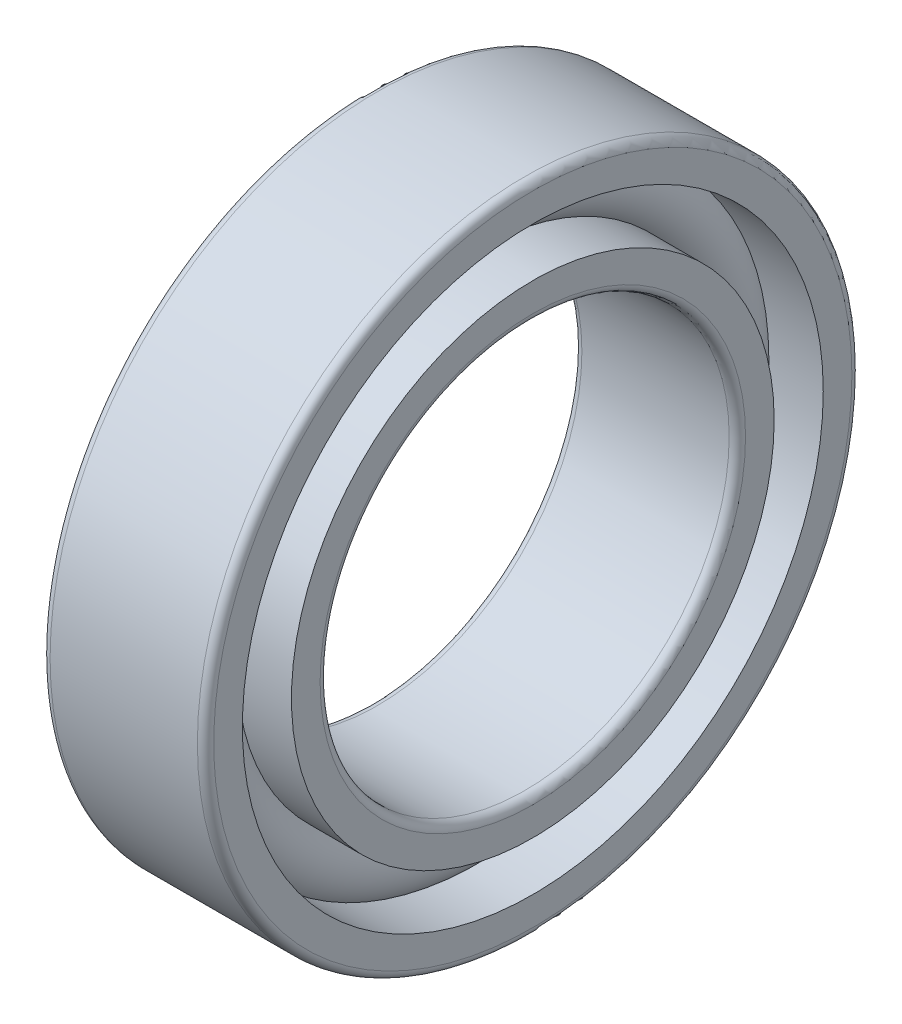
SolidWorks part; units mm, degrees
ref_plane "Plane1" through (0, 0, 0) normal (0, 0, 1) x (1, 0, 0)
ref_plane "Plane2" through (0, 0, 0) normal (0, 1, 0) x (1, 0, 0)
ref_plane "Plane3" through (0, 0, 0) normal (1, 0, 0) x (0, 0, -1)
sketch "Clipboard" plane through (0, 0, 0) normal (0, 0, 1) x (1, 0, 0)
  line L0 (-10, 0) -> (10, 0) construction
  line L1 (0, 0) -> (22.3471, -0.7804)
  line L2 (0, 0) -> (9.7441, 0.3403)
  line L3 (0, 0) -> (22.3471, -0.7804)
  line L4 (0, 0) -> (-22.3573, -0.3902)
sketch "CagSpiSke" plane through (0, 0, 0) normal (0, 0, 1) x (1, 0, 0)
  line L0 (0.135, 9.525) -> (0.135, 9.975)
  line L1 (0.135, 9.975) -> (-0.135, 9.975)
  line L2 (-0.135, 9.975) -> (-0.135, 9.525)
  line L3 (-0.135, 9.525) -> (0.135, 9.525)
  line L4 (-20.6375, 0) -> (20.6375, 0) construction
  line L5 (0, 0) -> (0, 23.7692) construction
revolve "CageSpine" add sketch "CagSpiSke" angle 0.001 about L4 reverse direction yes
ref_axis "Axis1" through (-50, 0, 0) along (1, 0, 0)
sketch "CagBalSke" plane through (0, 0, 0) normal (0, 0, 1) x (1, 0, 0)
  line L0 (-1.485, 9.75) -> (1.485, 9.75)
  line L1 (-1.905, 9.75) -> (1.905, 9.75) construction
  line L2 (-10, 0) -> (10, 0) construction
  line L3 (0, 0) -> (0, 24) construction
  arc A0 (1.485, 9.75) -> (-1.485, 9.75) centre (0, 9.75) cw
revolve "CageBall" [suppressed] add sketch "CagBalSke" angle 360 about L1 reverse direction yes
pattern_circular "CageBalls" [suppressed] count 2 every 180 about axis through (-50, 0, 0) along (1, 0, 0)
sketch "CagTrmODSke" plane through (0, 0, 0) normal (0, 0, 1) x (1, 0, 0)
  line L0 (1.486, 9.975) -> (1.486, 11.236)
  line L1 (1.486, 11.236) -> (-1.486, 11.236)
  line L2 (-1.486, 11.236) -> (-1.486, 9.975)
  line L3 (-1.486, 9.975) -> (1.486, 9.975)
  line L4 (-20.6375, 0) -> (20.6375, 0) construction
  line L5 (0, 0) -> (0, 25) construction
revolve "CageTrimOD" [suppressed] cut sketch "CagTrmODSke" angle 360 about L4 reverse direction yes
sketch "CagTrmIDSke" plane through (0, 0, 0) normal (0, 0, 1) x (1, 0, 0)
  line L0 (1.486, 8.266) -> (1.486, 9.525)
  line L1 (1.486, 9.525) -> (-1.486, 9.525)
  line L2 (-1.486, 9.525) -> (-1.486, 8.266)
  line L3 (-1.486, 8.266) -> (1.486, 8.266)
  line L4 (-20.6375, 0) -> (20.6375, 0) construction
  line L5 (0, 0) -> (0, 25) construction
revolve "CageTrimID" [suppressed] cut sketch "CagTrmIDSke" angle 360 about L4 reverse direction yes
sketch "BalSimSke" plane through (0, 0, 0) normal (0, 0, 1) x (1, 0, 0)
  line L0 (-10, 0) -> (10, 0) construction
  line L1 (-10, 9.75) -> (10, 9.75) construction
  line L2 (0, 0) -> (0, 23) construction
  circle A0 centre (0, 9.75) radius 1.35
revolve "BallsSimplified" add sketch "BalSimSke" angle 360 about L0
sketch "BalDetSke" plane through (0, 0, 0) normal (0, 0, 1) x (1, 0, 0)
  line L0 (-1.35, 9.75) -> (1.35, 9.75)
  line L1 (-1.905, 9.75) -> (1.905, 9.75) construction
  line L2 (0, 0) -> (0, 25) construction
  arc A0 (1.35, 9.75) -> (-1.35, 9.75) centre (0, 9.75) cw
revolve "BallDetailed" [suppressed] add sketch "BalDetSke" angle 360 about L1 reverse direction yes
sketch "InnRacSke" plane through (0, 0, 0) normal (0, 0, 1) x (1, 0, 0)
  line L0 (-0.9724, 8.85) -> (-3, 8.85)
  line L1 (-3, 8.85) -> (-3, 7.8)
  line L2 (-2.7, 7.5) -> (2.7, 7.5)
  line L3 (3, 7.8) -> (3, 8.85)
  line L4 (3, 8.85) -> (0.9724, 8.85)
  line L5 (-20.6375, 0) -> (20.6375, 0) construction
  line L6 (0, 0) -> (0, 30) construction
  arc A0 (-3, 7.8) -> (-2.7, 7.5) centre (-2.7, 7.8) ccw
  arc A1 (2.7, 7.5) -> (3, 7.8) centre (2.7, 7.8) ccw
  arc A2 (0.9724, 8.85) -> (-0.9724, 8.85) centre (0, 9.75) cw
  dimension "Fillet_radius" = 0.3
revolve "InnerRace" add sketch "InnRacSke" angle 360 about L5 reverse direction yes
sketch "OutRacSke" plane through (0, 0, 0) normal (0, 0, 1) x (1, 0, 0)
  line L0 (-0.9724, 10.65) -> (-3, 10.65)
  line L1 (-3, 10.65) -> (-3, 11.7)
  line L2 (-2.7, 12) -> (2.7, 12)
  line L3 (3, 11.7) -> (3, 10.65)
  line L4 (3, 10.65) -> (0.9724, 10.65)
  line L5 (-20.6375, 0) -> (20.6375, 0) construction
  line L6 (0, 0) -> (0, 30) construction
  arc A0 (-3, 11.7) -> (-2.7, 12) centre (-2.7, 11.7) cw
  arc A1 (2.7, 12) -> (3, 11.7) centre (2.7, 11.7) cw
  arc A2 (0.9724, 10.65) -> (-0.9724, 10.65) centre (0, 9.75) ccw
  dimension "Fillet_radius" = 0.3
revolve "OuterRace" add sketch "OutRacSke" angle 360 about L5 reverse direction yes
pattern_circular "BallsDetailed" [suppressed] count 2 every 180 about axis through (-50, 0, 0) along (1, 0, 0)
equation "\"BallCLRad@Clipboard\" = ( \"OD@OutRacSke\" + \"ID@InnRacSke\" ) / 4"
equation "\"BallCLRad@BalSimSke\" = \"BallCLRad@Clipboard\""
equation "\"BallCLRad@BalDetSke\" = \"BallCLRad@Clipboard\""
equation "\"BallCLRad@InnRacSke\" = \"BallCLRad@Clipboard\""
equation "\"BallCLRad@OutRacSke\" = \"BallCLRad@Clipboard\""
equation "\"Ball_diameter@InnRacSke\" = \"Ball_diameter@BalDetSke\" - 0.05"
equation "\"Ball_diameter@OutRacSke\" = \"Ball_diameter@BalDetSke\" - 0.05"
equation "\"Ball_diameter@BalSimSke\" = \"Ball_diameter@BalDetSke\""
equation "\"Width@OutRacSke\" = \"Width@InnRacSke\""
equation "\"Fillet_radius@OutRacSke\" = \"Fillet_radius@InnRacSke\""
equation "\"Max_count@Clipboard\" = int( 3.14159265 / atn(( \"Ball_diameter@BalDetSke\" / 2) / sqr( \"BallCLRad@Clipboard\"  *  \"BallCLRad@Clipboard\" - ( \"Ball_diameter@BalDetSke\" / 2) *  ( \"Ball_diameter@BalDetSke\" / 2))))"
equation "\"Max_count@Clipboard\" = ((sgn( \"Max_count@Clipboard\" - \"Count@Clipboard\" )-1)*( \"Max_count@Clipboard\" - \"Count@Clipboard\" ))/-2+ \"Count@Clipboard\""
equation "\"Count@BallsDetailed\" = int( \"Show_count@Clipboard\" ) "
equation "\"Count@BallsDetailed\" = ((sgn( \"Count@BallsDetailed\" - \"Max_count@Clipboard\" )-1)*( \"Count@BallsDetailed\" - \"Max_count@Clipboard\" ))/-2+ \"Max_count@Clipboard\""
equation "\"Count@BallsDetailed\" = ((sgn( \"Count@BallsDetailed\" - \"Min_count@Clipboard\" )+1)*( \"Count@BallsDetailed\" - \"Min_count@Clipboard\"))/2 +\"Min_count@Clipboard\""
equation "\"Angle@BallsDetailed\" = 360.0 / \"Max_count@Clipboard\""
equation "\"BallCLRad@CagBalSke\" = \"BallCLRad@Clipboard\""
equation "\"Count@CageBalls\" = \"Count@BallsDetailed\""
equation "\"Angle@CageBalls\" = \"Angle@BallsDetailed\""
equation "\"Angle@CageSpine\" =  \"Angle@CageBalls\" * ( \"Count@CageBalls\" -1 + int( \"Count@CageBalls\" / \"Max_count@Clipboard\" ) )  + 0.001 -  int( \"Count@CageBalls\" / \"Max_count@Clipboard\" ) * 0.001"
equation "\"Angle@CageSpine\" =  \"Angle@CageSpine\" * int( \"Min_count@Clipboard\" / 2) + int(1 / \"Min_count@Clipboard\")  * 0.001"
equation "\"CageWallOD@CagBalSke\" =  \"Ball_diameter@BalDetSke\" * 1.1"
equation "\"Thickness@CagSpiSke\" =  \"Ball_diameter@BalDetSke\" * 0.1"
equation "\"OD@CagTrmODSke\" = \"BallCLRad@Clipboard\" * 2 + \"CageWallOD@CagBalSke\" + 0.002"
equation "\"ID@CagTrmODSke\" = \"BallCLRad@Clipboard\" * 2 + \"Ball_diameter@BalDetSke\" / 6"
equation "\"OD@CagTrmIDSke\" = \"BallCLRad@Clipboard\" * 2 - \"Ball_diameter@BalDetSke\" / 6"
equation "\"ID@CagTrmIDSke\" = \"BallCLRad@Clipboard\" * 2 - \"CageWallOD@CagBalSke\" + 0.002"
equation "\"OD@CagSpiSke\" = \"ID@CagTrmODSke\""
equation "\"ID@CagSpiSke\" = \"OD@CagTrmIDSke\""
equation "\"Width@CagTrmODSke\" = \"CageWallOD@CagBalSke\" + 0.002"
equation "\"Width@CagTrmIDSke\" = \"CageWallOD@CagBalSke\" + 0.002"
